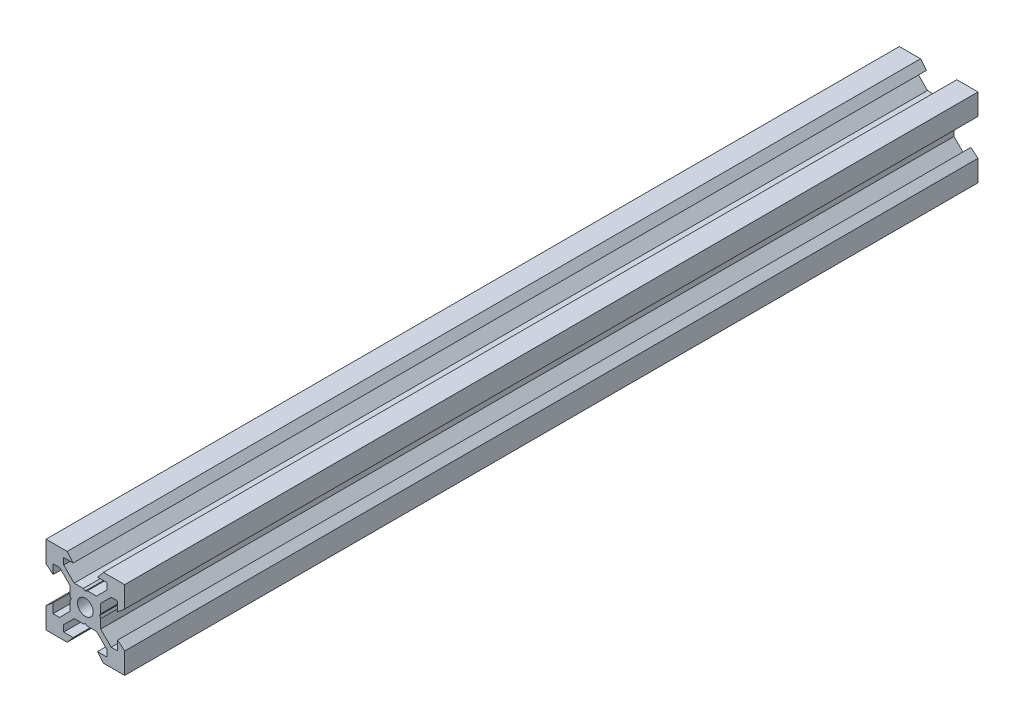
SolidWorks part; units mm, degrees
ref_plane "Front Plane" through (0, 0, 0) normal (0, 0, 1) x (1, 0, 0)
ref_plane "Top Plane" through (0, 0, 0) normal (0, 1, 0) x (1, 0, 0)
ref_plane "Right Plane" through (0, 0, 0) normal (1, 0, 0) x (0, 0, -1)
sketch "Sketch1" plane through (0, 0, 0) normal (0, 0, 1) x (1, 0, 0)
  line L0 (10, 10) -> (4.6104, 10) construction
  line L1 (10, 10) -> (10, 4.6104) construction
  line L2 (10, -10) -> (10, -4.6104) construction
  line L3 (10, -10) -> (4.6104, -10) construction
  line L4 (10, 10) -> (10, 4.6104)
  line L5 (6.5607, 5.5) -> (8.2, 5.5)
  line L6 (5.5, 8.2) -> (5.5, 6.5607)
  line L7 (10, 10) -> (4.6104, 10)
  line L8 (10, 10) -> (10, 4.6104)
  line L9 (6.5607, 5.5) -> (3.9, 2.8393)
  line L10 (5.5, 6.5607) -> (2.8393, 3.9)
  line L11 (10, 4.6104) -> (8.2, 3.1)
  line L12 (4.6104, 10) -> (3.1, 8.2)
  line L13 (8.2, 3.1) -> (8.2, 5.5)
  line L14 (3.1, 8.2) -> (5.5, 8.2)
  line L15 (-6.5607, 5.5) -> (-8.2, 5.5)
  line L16 (6.5607, -5.5) -> (8.2, -5.5)
  line L17 (3.1, -8.2) -> (5.5, -8.2)
  line L18 (8.2, -3.1) -> (8.2, -5.5)
  line L19 (4.6104, -10) -> (3.1, -8.2)
  line L20 (10, -4.6104) -> (8.2, -3.1)
  line L21 (0.5196, -3.9) -> (0, -3.6)
  line L22 (0.5196, 3.9) -> (0, 3.6)
  line L23 (3.6, 0) -> (3.9, -0.5196)
  line L24 (3.9, 0.5196) -> (3.6, 0)
  line L25 (3.9, 0.5196) -> (3.9, 2.8393)
  line L26 (2.8393, 3.9) -> (0.5196, 3.9)
  line L27 (3.9, -2.8393) -> (3.9, -0.5196)
  line L28 (2.8393, -3.9) -> (0.5196, -3.9)
  line L29 (5.5, -6.5607) -> (2.8393, -3.9)
  line L30 (6.5607, -5.5) -> (3.9, -2.8393)
  line L31 (10, -10) -> (10, -4.6104)
  line L32 (10, -10) -> (4.6104, -10)
  line L33 (5.5, -8.2) -> (5.5, -6.5607)
  line L34 (-6.5607, -5.5) -> (-8.2, -5.5)
  line L35 (10, -10) -> (10, -4.6104)
  line L36 (0, 0) -> (0, 8.2) construction
  line L37 (-10, -10) -> (-4.6104, -10) construction
  line L38 (-10, -10) -> (-10, -4.6104) construction
  line L39 (-10, 10) -> (-10, 4.6104) construction
  line L40 (-10, 10) -> (-4.6104, 10) construction
  line L41 (-10, -10) -> (-10, -4.6104)
  line L43 (-5.5, -8.2) -> (-5.5, -6.5607)
  line L44 (-10, -10) -> (-4.6104, -10)
  line L45 (-10, -10) -> (-10, -4.6104)
  line L46 (-6.5607, -5.5) -> (-3.9, -2.8393)
  line L47 (-5.5, -6.5607) -> (-2.8393, -3.9)
  line L48 (-2.8393, -3.9) -> (-0.5196, -3.9)
  line L49 (-3.9, -2.8393) -> (-3.9, -0.5196)
  line L50 (-2.8393, 3.9) -> (-0.5196, 3.9)
  line L51 (-3.9, 0.5196) -> (-3.9, 2.8393)
  line L52 (-3.9, 0.5196) -> (-3.6, 0)
  line L53 (-3.6, 0) -> (-3.9, -0.5196)
  line L54 (-0.5196, 3.9) -> (0, 3.6)
  line L55 (-0.5196, -3.9) -> (0, -3.6)
  line L56 (-10, -4.6104) -> (-8.2, -3.1)
  line L57 (-4.6104, -10) -> (-3.1, -8.2)
  line L58 (-8.2, -3.1) -> (-8.2, -5.5)
  line L59 (-3.1, -8.2) -> (-5.5, -8.2)
  line L60 (-10, -10) -> (10, -10) construction
  line L61 (-10, -10) -> (-10, 10) construction
  line L62 (-3.1, 8.2) -> (-5.5, 8.2)
  line L63 (-8.2, 3.1) -> (-8.2, 5.5)
  line L64 (-4.6104, 10) -> (-3.1, 8.2)
  line L65 (-10, 4.6104) -> (-8.2, 3.1)
  line L66 (-5.5, 6.5607) -> (-2.8393, 3.9)
  line L67 (-6.5607, 5.5) -> (-3.9, 2.8393)
  line L68 (-10, 10) -> (-10, 4.6104)
  line L69 (-10, 10) -> (-4.6104, 10)
  line L70 (-5.5, 8.2) -> (-5.5, 6.5607)
  line L71 (-10, 10) -> (10, 10) construction
  line L72 (-10, 10) -> (-10, 4.6104)
  line L73 (10, -10) -> (10, 10) construction
  line L74 (-10, -10) -> (10, 10) construction
  line L75 (-10, 10) -> (10, -10) construction
  circle A0 centre (0, 0) radius 2
  dimension "D7" = 4
  dimension "D1" = 20
  dimension "D2" = 5.3896
  dimension "D3" = 4.5
  dimension "D4" = 50
  dimension "D5" = 1.8
  dimension "D6" = 1.5104
  dimension "D8" = 5.5
  dimension "D9" = 120
  dimension "D10" = 0.3
  dimension "D11" = 2.3197
  dimension "D12" = 7.8
  dimension "D13" = 7.8
  dimension "D14" = 1.5
  dimension "D15" = 2.6607
extrude "Boss-Extrude1" add sketch "Sketch1" along normal mid plane 216.89 contours L70 L62 L64 L69 L68 L65 L63 L15 L67 L51 L52 L53 L49 L46 L34 L58 L56 L41 L44 L57 L59 L43 L47 L48 L55 L21 L28 L29 L33 L17 L19 L32 L31 L20 L18 L16 L30 L27 L23 L24 L25 L9 L5 L13 L11 L4 L7 L12 L14 L6 L10 region at (9.7172, 7.3052, 0)
